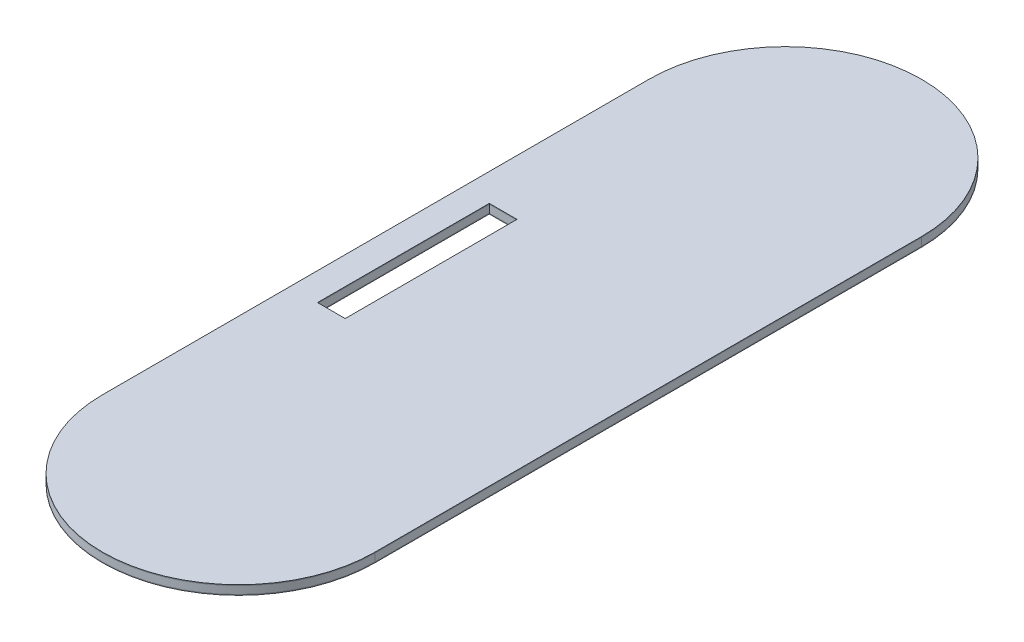
SolidWorks part; units mm, degrees
ref_plane "Front Plane" through (0, 0, 0) normal (0, 0, 1) x (1, 0, 0)
ref_plane "Top Plane" through (0, 0, 0) normal (0, 1, 0) x (1, 0, 0)
ref_plane "Right Plane" through (0, 0, 0) normal (1, 0, 0) x (0, 0, -1)
sketch "Sketch1" plane through (0, 0, 0) normal (0, 1, 0) x (1, 0, 0)
  line L0 (0, -88.9) -> (0, 88.9) construction
  line L2 (44.323, 88.9) -> (44.323, -88.9)
  line L3 (0, 0) -> (-35.323, 0) construction
  line L8 (-35.323, -27.94) -> (-35.323, 27.94)
  line L11 (-35.323, 27.94) -> (-26.323, 27.94)
  line L12 (-26.323, 27.94) -> (-26.323, -27.94)
  line L13 (-26.323, -27.94) -> (-35.323, -27.94)
  line L14 (-44.323, 88.9) -> (-44.323, -88.9)
  arc A0 (44.323, 88.9) -> (-44.323, 88.9) centre (0, 88.9) ccw
  arc A1 (-44.323, -88.9) -> (44.323, -88.9) centre (0, -88.9) ccw
  point P8 (0, 0)
  point P13 (-89.4761, 0)
  point P18 (-35.323, 0)
  dimension "D2" = 88.646
  dimension "D1" = 177.8
  dimension "D3" = 55.88
  dimension "D4" = 9
extrude "Boss-Extrude1" add sketch "Sketch1" along normal blind 0.25
sketch "Sketch2" plane through (0, 0.25, 0) normal (0, 1, 0) x (1, 0, 0)
  line L0 (-26.323, 27.94) -> (-35.323, 27.94) construction
  line L1 (-35.323, 27.94) -> (-35.323, -27.94) construction
  line L2 (-44.323, 88.9) -> (-44.323, -88.9)
  line L3 (44.323, -88.9) -> (44.323, 88.9)
  line L4 (-44.323, 88.9) -> (-44.323, -88.9)
  line L5 (44.323, -88.9) -> (44.323, 88.9)
  line L6 (-35.323, -27.94) -> (-26.323, -27.94) construction
  line L7 (-26.323, -27.94) -> (-26.323, 27.94) construction
  line L8 (-26.323, 27.94) -> (-35.323, 27.94)
  line L9 (-35.323, 27.94) -> (-35.323, -27.94)
  line L10 (-35.323, -27.94) -> (-26.323, -27.94)
  line L11 (-26.323, -27.94) -> (-26.323, 27.94)
  arc A2 (44.323, 88.9) -> (-44.323, 88.9) centre (0, 88.9) ccw
  arc A3 (-44.323, -88.9) -> (44.323, -88.9) centre (0, -88.9) ccw
  arc A4 (44.323, 88.9) -> (-44.323, 88.9) centre (0, 88.9) ccw
  arc A5 (-44.323, -88.9) -> (44.323, -88.9) centre (0, -88.9) ccw
  arc M5 (44.323, 88.9) -> (-44.323, 88.9) centre (0, 88.9) ccw
  line M6 (-44.323, 88.9) -> (-44.323, -88.9)
  arc M7 (-44.323, -88.9) -> (44.323, -88.9) centre (0, -88.9) ccw
  line M8 (44.323, -88.9) -> (44.323, 88.9)
  line M9 (-35.323, 27.94) -> (-26.323, 27.94)
  line M10 (-26.323, 27.94) -> (-26.323, -27.94)
  line M11 (-26.323, -27.94) -> (-35.323, -27.94)
  line M12 (-35.323, -27.94) -> (-35.323, 27.94)
  dimension "D1" = 0
extrude "Boss-Extrude3" add sketch "Sketch2" along normal blind 2.5 separate body contours M8 M5 M6 M7 M12 M9 M10 M11 region at (0.7234, 0.25, 0)
sketch "Sketch3" plane through (0, 2.75, 0) normal (0, 1, 0) x (1, 0, 0)
  line L4 (-35.323, 27.94) -> (-35.323, -27.94)
  line L5 (-26.323, 27.94) -> (-35.323, 27.94)
  line L6 (-26.323, -27.94) -> (-26.323, 27.94)
  line L7 (-35.323, -27.94) -> (-26.323, -27.94)
  line L8 (-35.323, 27.94) -> (-35.323, -27.94)
  line L9 (-26.323, 27.94) -> (-35.323, 27.94)
  line L10 (-26.323, -27.94) -> (-26.323, 27.94)
  line L11 (-35.323, -27.94) -> (-26.323, -27.94)
  line M5 (-35.323, -27.94) -> (-35.323, 27.94)
  line M6 (-35.323, 27.94) -> (-26.323, 27.94)
  line M7 (-26.323, 27.94) -> (-26.323, -27.94)
  line M8 (-26.323, -27.94) -> (-35.323, -27.94)
  line M9 (44.323, -88.9) -> (44.323, 88.9)
  arc M10 (44.323, 88.9) -> (-44.323, 88.9) centre (0, 88.9) ccw
  line M11 (-44.323, 88.9) -> (-44.323, -88.9)
  arc M12 (-44.323, -88.9) -> (44.323, -88.9) centre (0, -88.9) ccw
  dimension "D1" = 0
extrude "Boss-Extrude4" add sketch "Sketch3" along normal blind 0.25 separate body contours M12 M9 M10 M11 M8 M5 M6 M7 region at (0.7234, 2.75, 0)
